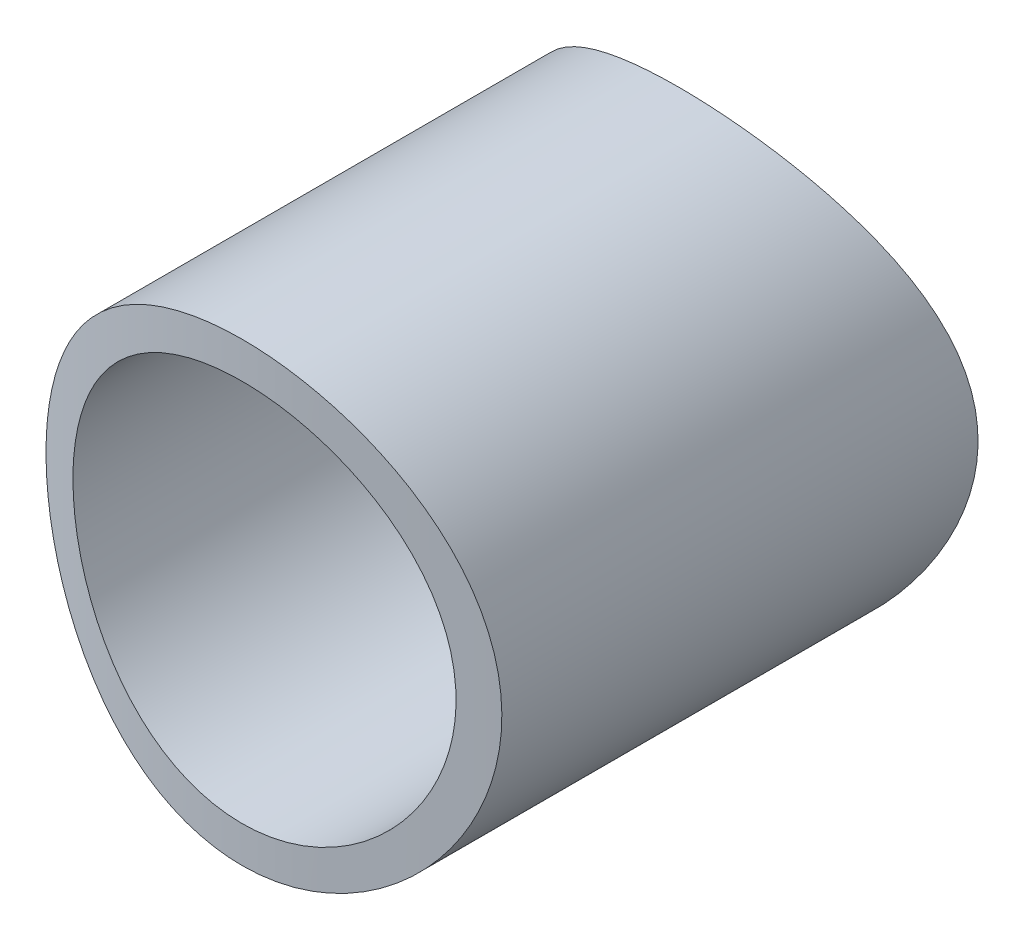
SolidWorks part; units mm, degrees
material "PTFE (general)"
ref_plane "Front Plane" through (0, 0, 0) normal (0, 0, 1) x (1, 0, 0)
ref_plane "Top Plane" through (0, 0, 0) normal (0, 1, 0) x (1, 0, 0)
ref_plane "Right Plane" through (0, 0, 0) normal (1, 0, 0) x (0, 0, -1)
sketch "Sketch1" plane through (0, 0, 0) normal (0, 0, 1) x (1, 0, 0)
  circle A0 centre (0, 0) radius 10.53
  circle A1 centre (0, 0) radius 12.53
  dimension "D1" = 21.06
  dimension "D2" = 2
extrude "Boss-Extrude1" add sketch "Sketch1" along normal blind 60
sketch "Sketch2" plane through (0, 0, 0) normal (0, 1, 0) x (1, 0, 0)
  circle A0 centre (0, 0) radius 22
  circle A1 centre (0, 0) radius 46
  circle A2 centre (0, 0) radius 74.5897
  dimension "D1" = 44
  dimension "D2" = 92
extrude "Cut-Extrude1" cut sketch "Sketch2" against normal through all both and the other way through all contours A2 A1 | A0 region at (0, 0, 0) region at (-72.48, 0, 0)
